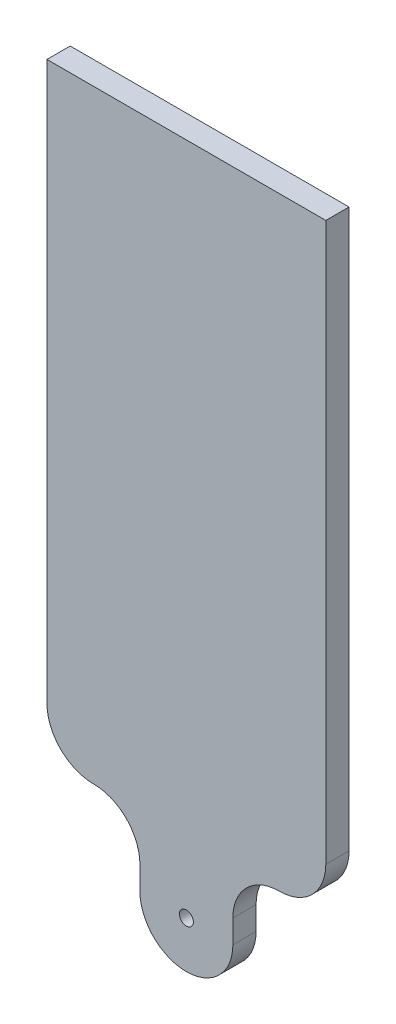
SolidWorks part; units mm, degrees
material "Acrílico (médio-alto impacto)"
ref_plane "Plano frontal" through (0, 0, 0) normal (0, 0, 1) x (1, 0, 0)
ref_plane "Plano superior" through (0, 0, 0) normal (0, 1, 0) x (1, 0, 0)
ref_plane "Plano direito" through (0, 0, 0) normal (1, 0, 0) x (0, 0, -1)
sketch "Esboço1" plane through (0, 0, 0) normal (0, 0, 1) x (1, 0, 0)
  line L0 (-14.0897, 13.1354) -> (-14.0897, 28.1354)
  line L1 (5.9103, 13.1354) -> (5.9103, 28.1354)
  line L2 (5.9103, 28.1354) -> (25.9103, 28.1354)
  line L3 (-34.0897, 158.1354) -> (25.9103, 158.1354)
  line L4 (-34.0897, 158.1354) -> (-34.0897, 28.1354)
  line L5 (-34.0897, 28.1354) -> (-14.0897, 28.1354)
  line L6 (25.9103, 158.1354) -> (25.9103, 28.1354)
  arc A0 (-14.0897, 13.1354) -> (5.9103, 13.1354) centre (-4.0897, 13.1354) ccw
  dimension "D1" = 20
  dimension "D2" = 130
  dimension "D3" = 20
  dimension "D4" = 20
extrude "Ressalto-extrusão1" add sketch "Esboço1" along normal blind 5
sketch "Esboço2" plane through (0, 0, 5) normal (0, 0, 1) x (1, 0, 0)
  circle A0 centre (-4.0897, 13.1354) radius 1.5
  dimension "D1" = 3
extrude "Corte-extrusão1" cut sketch "Esboço2" against normal blind 5
fillet "Filete1" radius 10 4 edges at (5.9103, 28.1354, 2.5) (25.9103, 28.1354, 2.5) (-34.0897, 28.1354, 2.5) (-14.0897, 28.1354, 2.5)
